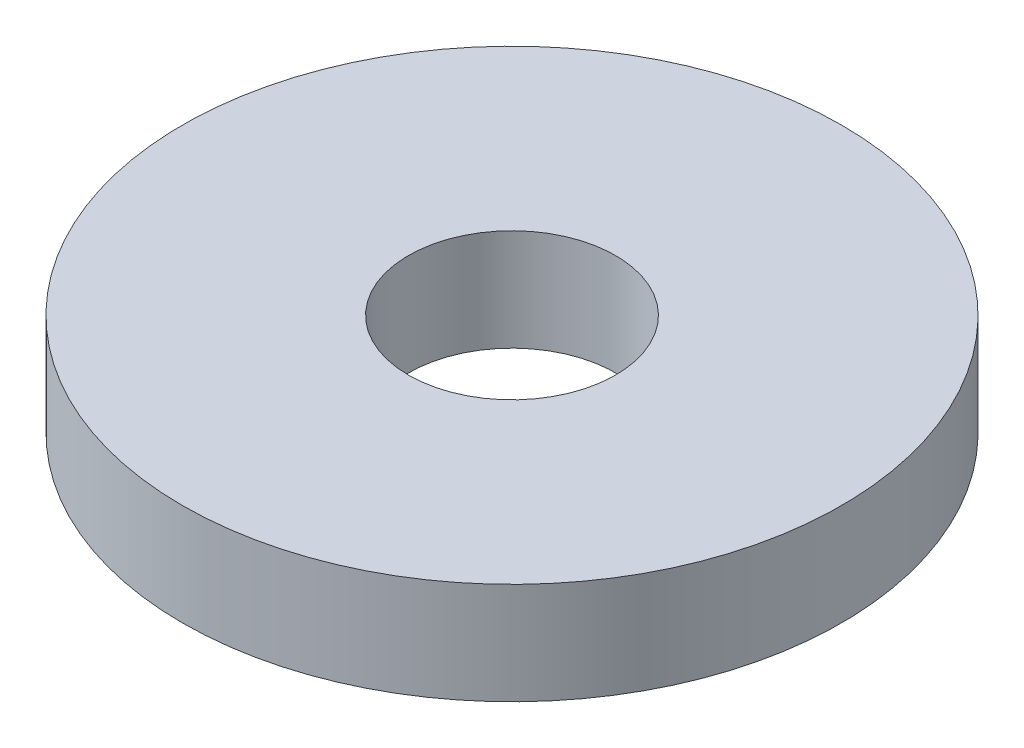
SolidWorks part; units mm, degrees
ref_plane "Front Plane" through (0, 0, 0) normal (0, 0, 1) x (1, 0, 0)
ref_plane "Top Plane" through (0, 0, 0) normal (0, 1, 0) x (1, 0, 0)
ref_plane "Right Plane" through (0, 0, 0) normal (1, 0, 0) x (0, 0, -1)
sketch "Sketch1" plane through (0, 0, 0) normal (0, 1, 0) x (1, 0, 0)
  circle A0 centre (0, 0) radius 87.5
  dimension "FLANGE_OD" = 175
extrude "Boss-Extrude1" add sketch "Sketch1" along normal blind 27
sketch "Sketch2" plane through (0, 0, 0) normal (0, 1, 0) x (1, 0, 0)
  circle A0 centre (0, 0) radius 27.5
  dimension "BORE_D" = 55
extrude "Cut-Extrude1" cut sketch "Sketch2" along normal through all
sketch "Sketch3" plane through (0, 27, 0) normal (0, 1, 0) x (1, 0, 0)
  circle A0 centre (0, 0) radius 19.5096 construction
  circle A1 centre (-19.5096, 0) radius 5.5869
  dimension "BOLT_D" = 11.1737
  dimension "BOLT_PCD" = 39.0192
extrude "Cut-Extrude2" cut sketch "Sketch3" against normal blind 18.6687 rebuild error yes
pattern_circular "CirPattern1" count 4 over 360 rebuild error yes
